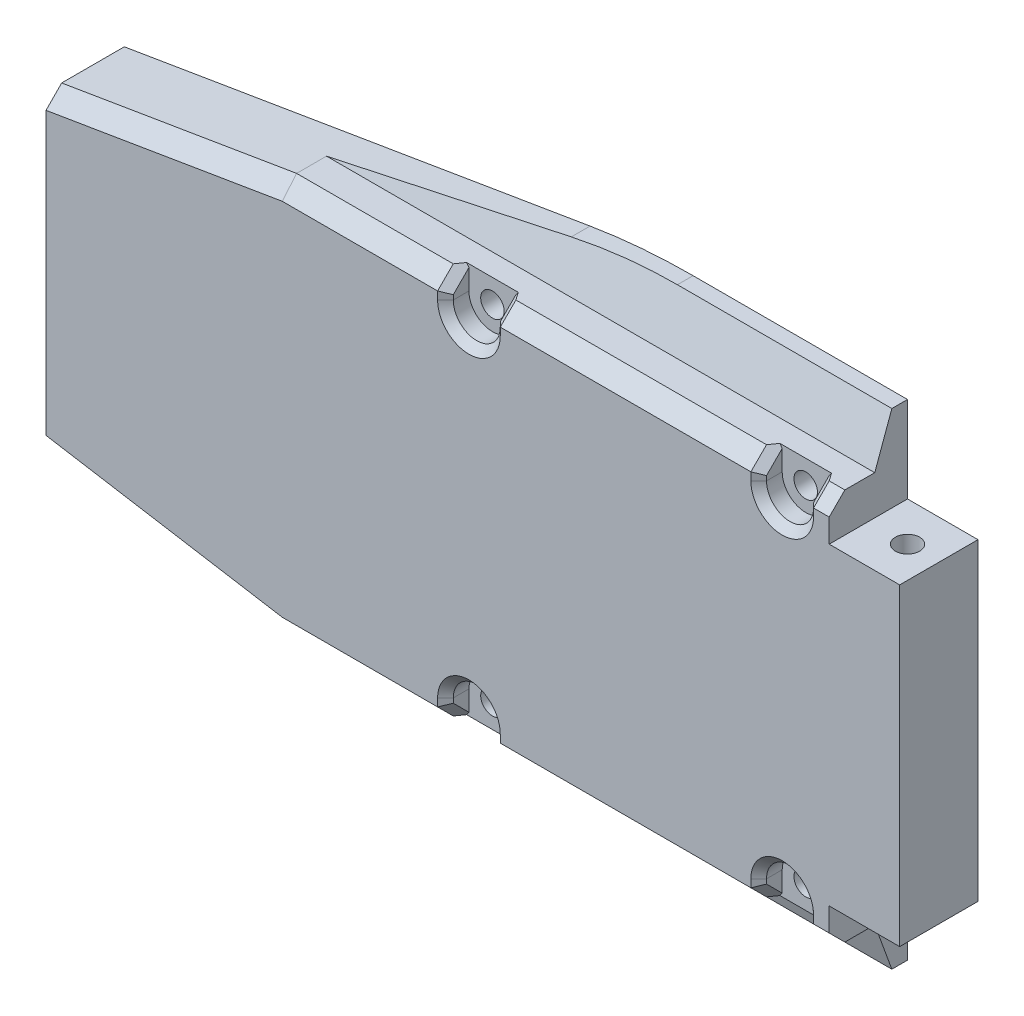
SolidWorks part; units mm, degrees
material "ABS"
ref_plane "Ebene vorne" through (0, 0, 0) normal (0, 0, 1) x (1, 0, 0)
ref_plane "Ebene oben" through (0, 0, 0) normal (0, 1, 0) x (1, 0, 0)
ref_plane "Ebene rechts" through (0, 0, 0) normal (1, 0, 0) x (0, 0, -1)
sketch "Skizze2" plane through (0, 0, 0) normal (0, 0, 1) x (1, 0, 0)
  line L0 (-151.7782, 0) -> (154.8922, 0) construction
  line L1 (0, 106.9611) -> (0, -93.0562) construction
  line L2 (0, 25) -> (-79, 25)
  line L3 (-79, 25) -> (-109, 20)
  line L4 (-109, 20) -> (-109, 11)
  line L5 (-109, 11) -> (-102, 11)
  line L6 (-99, 8) -> (-99, -8)
  line L7 (0, 25) -> (0, -25)
  line L8 (-109, -11) -> (-102, -11)
  line L9 (-109, -20) -> (-109, -11)
  line L10 (-79, -25) -> (-109, -20)
  line L11 (0, -25) -> (-79, -25)
  arc A0 (-102, -11) -> (-99, -8) centre (-102, -8) ccw
  arc A1 (-99, 8) -> (-102, 11) centre (-102, 8) ccw
  point P13 (0, 0)
  point P14 (-99, 0)
  point P19 (-99, -11)
  point P22 (-99, 11)
  dimension "D7" = 3
  dimension "D1" = 109
  dimension "D2" = 50
  dimension "D3" = 40
  dimension "D4" = 30
  dimension "D5" = 22
  dimension "D6" = 10
extrude "Aufsatz-Linear austragen1" add sketch "Skizze2" along normal blind 5 and the other way blind 5
hole_wizard "Ø3.1 (3.1) Durchmesser Bohrung1" positions "Skizze4" profile "Skizze3" hole size "Ø3.1" standard "ANSI Metrisch"
sketch "Skizze4" plane through (-109, 0, 0) normal (-1, 0, 0) x (0, 0, 1)
  line L0 (0, 37.8153) -> (0, -33.0973) construction
  line L3 (-22.117, 0) -> (22.0161, 0) construction
  point P0 (0, 15)
  point P14 (0, -15)
  dimension "D1" = 30
sketch "Skizze3" plane through (-109, 15, 0) normal (0, 1, 0) x (0, 0, 1)
  line L0 (0, 0) -> (0, 8.9313)
  line L1 (0, 8.9313) -> (1.55, 8)
  line L2 (1.55, 8) -> (1.55, 0)
  line L5 (1.55, 0) -> (0, 0)
  line L10 (0, 8.9313) -> (-1.55, 8) construction
  line L11 (0, -6.35) -> (0, 107.95) construction
  dimension "Bohrerdurchmesser" = 3.1
  dimension "Bohrungstiefe" = 8
  dimension "Spitzenwinkel" = 118
sketch "Skizze5" plane through (0, 0, 0) normal (0, 0, 1) x (1, 0, 0)
  line L0 (-134.3407, 0) -> (33.9152, 0) construction
  line L1 (0, 49.9151) -> (0, -37.4044) construction
  circle A0 centre (-55, 22) radius 1.5
  circle A1 centre (-15, 22) radius 1.5
  circle A2 centre (-15, -22) radius 1.5
  circle A3 centre (-55, -22) radius 1.5
  dimension "D1" = 3
  dimension "D2" = 40
  dimension "D3" = 15
  dimension "D4" = 22
extrude "Schnitt-Linear austragen1" cut sketch "Skizze5" against normal through all and the other way through all
sketch "Skizze6" plane through (0, 0, 5) normal (0, 0, 1) x (1, 0, 0)
  line L0 (-55, 22) -> (-55, 29.2626) construction
  line L1 (-58, 22) -> (-58, 29.2626)
  line L2 (-52, 22) -> (-52, 29.2626)
  line L3 (-15, 22) -> (-15, 29.2626) construction
  line L4 (-18, 22) -> (-18, 29.2626)
  line L5 (-12, 22) -> (-12, 29.2626)
  line L6 (-55, -22) -> (-55, -29.7807) construction
  line L7 (-52, -22) -> (-52, -29.7807)
  line L8 (-58, -22) -> (-58, -29.7807)
  line L9 (-15, -22) -> (-15, -30.8486) construction
  line L10 (-12, -22) -> (-12, -30.8486)
  line L11 (-18, -22) -> (-18, -30.8486)
  arc A4 (-58, 22) -> (-52, 22) centre (-55, 22) ccw
  arc A5 (-52, 29.2626) -> (-58, 29.2626) centre (-55, 29.2626) ccw
  arc A6 (-18, 22) -> (-12, 22) centre (-15, 22) ccw
  arc A7 (-12, 29.2626) -> (-18, 29.2626) centre (-15, 29.2626) ccw
  arc A8 (-52, -22) -> (-58, -22) centre (-55, -22) ccw
  arc A9 (-58, -29.7807) -> (-52, -29.7807) centre (-55, -29.7807) ccw
  arc A10 (-12, -22) -> (-18, -22) centre (-15, -22) ccw
  arc A11 (-18, -30.8486) -> (-12, -30.8486) centre (-15, -30.8486) ccw
  point P6 (-15, 25.6313)
  point P12 (-55, 25.6313)
  point P19 (-55, -25.8903)
  point P28 (-15, -26.4243)
  dimension "D1" = 3
extrude "Schnitt-Linear austragen2" cut sketch "Skizze6" against normal blind 3
sketch "Skizze7" plane through (0, 0, 5) normal (0, 0, 1) x (1, 0, 0)
  line L0 (-130.6386, 0) -> (13.2343, 0) construction
  line L1 (0, 46.5959) -> (0, -35.1065) construction
  line L2 (0, 25) -> (-9, 25)
  line L3 (0, 25) -> (-12, 25) construction
  line L4 (-9, 25) -> (-9, 20)
  line L5 (-9, 20) -> (0, 20)
  line L6 (0, 20) -> (0, 25)
  line L7 (0, -20) -> (0, -25)
  line L8 (-9, -20) -> (0, -20)
  line L9 (-9, -25) -> (-9, -20)
  line L10 (0, -25) -> (-9, -25)
  dimension "D1" = 5
  dimension "D2" = 9
extrude "Schnitt-Linear austragen3" cut sketch "Skizze7" against normal through all and the other way through all
sketch "Skizze8" plane through (0, 0, 0) normal (0, 0, 1) x (1, 0, 0)
  line L0 (-143.7875, 0) -> (29.5748, 0) construction
  line L1 (0, 40.8512) -> (0, -33.9576) construction
  line L17 (-55, 30.597) -> (-55, -26.6464) construction
  line L18 (-51, -22) -> (-19, -22)
  line L19 (-56, 18.127) -> (-56, -18.127)
  line L20 (-54, 18.127) -> (-54, -18.127)
  line L21 (-59, -22) -> (-78.7517, -22)
  line L22 (-78.7517, -22) -> (-97, -18.9586)
  line L23 (-97, -18.9586) -> (-97, 18.9586)
  line L24 (-79, -25) -> (-58, -25) construction
  line L25 (-109, -20) -> (-79, -25) construction
  line L26 (-99, 8) -> (-99, -8) construction
  line L27 (-78.7517, 22) -> (-97, 18.9586)
  line L28 (-59, 22) -> (-78.7517, 22)
  line L29 (-51, 22) -> (-19, 22)
  line L30 (-15, -18) -> (-7, -18)
  line L31 (-7, -18) -> (-7, 18)
  line L32 (-15, 18) -> (-7, 18)
  arc A6 (-56, -18.127) -> (-59, -22) centre (-55, -22) ccw
  arc A7 (-54, -18.127) -> (-51, -22) centre (-55, -22) cw
  arc A8 (-54, 18.127) -> (-51, 22) centre (-55, 22) ccw
  arc A9 (-56, 18.127) -> (-59, 22) centre (-55, 22) cw
  arc A10 (-19, -22) -> (-15, -18) centre (-15, -22) cw
  arc A11 (-19, 22) -> (-15, 18) centre (-15, 22) ccw
  point P16 (-56, 0)
  point P29 (-97, 0)
  point P30 (-54, 0)
  point P41 (-7, 0)
  dimension "D3" = 4
  dimension "D1" = 2
  dimension "D2" = 3
  dimension "D4" = 2
  dimension "D5" = 3
  dimension "D6" = 7
extrude "Schnitt-Linear austragen4" cut sketch "Skizze8" against normal through all and the other way blind 4
sketch "Skizze9" plane through (0, 0, -5) normal (0, 0, -1) x (-1, 0, 0)
  line L0 (-28.3161, 0) -> (120.4033, 0) construction
  line L1 (0, 48.4649) -> (0, -32.3525) construction
  line L2 (9, 25) -> (9, 31)
  line L3 (9, 31) -> (43, 31)
  line L7 (9, 25) -> (79, 25)
  line L8 (9, -25) -> (79, -25)
  line L11 (9, -31) -> (43, -31)
  line L12 (9, -25) -> (9, -31)
  line L13 (43, 31) -> (79, 25)
  line L14 (43, -31) -> (79, -25)
  line L15 (79, 25) -> (109, 20) construction
  dimension "D1" = 6
extrude "Aufsatz-Linear austragen2" add sketch "Skizze9" against normal blind 2
hole_wizard "Ø3.1 (3.1) Durchmesser Bohrung2" positions "Skizze11" profile "Skizze10" hole size "Ø3.1" standard "ANSI Metrisch"
sketch "Skizze11" plane through (0, 20, 0) normal (0, 1, 0) x (1, 0, 0)
  line L0 (14.2177, 0) -> (-26.5383, 0) construction
  point P0 (-4, 0)
  dimension "D1" = 4
sketch "Skizze10" plane through (-4, 20, 0) normal (1, 0, 0) x (0, 0, 1)
  line L0 (0, 0) -> (0, 10.9313)
  line L1 (0, 10.9313) -> (1.55, 10)
  line L2 (1.55, 10) -> (1.55, 0)
  line L5 (1.55, 0) -> (0, 0)
  line L10 (0, 10.9313) -> (-1.55, 10) construction
  line L11 (0, -6.35) -> (0, 107.95) construction
  dimension "Bohrerdurchmesser" = 3.1
  dimension "Bohrungstiefe" = 10
  dimension "Spitzenwinkel" = 118
mirror "Spiegeln1" about plane through (0, 0, 0) normal (0, 1, 0) of "Ø3.1 (3.1) Durchmesser Bohrung2"
chamfer "Fase1" distance 6 angle 20 1 edges at (-44, 25, -3) first distance on face at (-35, 28, -3)
chamfer "Fase2" distance 6 angle 20 1 edges at (-44, -25, -3) first distance on face at (-35, -28, -3)
fillet "Verrundung1" radius 80 2 edges at (-43, 31, -4) (-43, -31, -4)
fillet "Verrundung2" radius 2 14 edges at (-7, 18, -0.5) (-19, 22, -0.5) (-51, 22, -0.5) (-54, 18.127, -0.5) (-56, 18.127, -0.5) (-59, 22, -0.5) (-97, 18.9586, -0.5) (-97, -18.9586, -0.5) (-59, -22, -0.5) (-56, -18.127, -0.5) (-54, -18.127, -0.5) (-51, -22, -0.5) (-19, -22, -0.5) (-7, -18, -0.5)
sketch "Skizze12" plane through (0, 0, 5) normal (0, 0, 1) x (1, 0, 0)
  line L0 (-110.4008, 0) -> (7.7355, 0) construction
  line L1 (0, 42.6084) -> (0, -37.939) construction
  line L2 (-109, 11) -> (-109, -11)
  line L3 (-109, -11) -> (-99, -11)
  line L4 (-99, -11) -> (-99, 11)
  line L5 (-99, 11) -> (-109, 11)
  line L6 (-109, 20) -> (-109, 11) construction
  line L7 (-99, 8) -> (-99, -8) construction
extrude "Aufsatz-Linear austragen3" add sketch "Skizze12" against normal blind 1
chamfer "Fase3" distance 2 angle 45 8 edges at (-10.5, -25, 5) (-35, -25, 5) (-68.5, -25, 5) (-94, -22.5, 5) (-10.5, 25, 5) (-35, 25, 5) (-68.5, 25, 5) (-94, 22.5, 5)
fillet "Verrundung3" [suppressed] radius 1.5
sketch "Skizze13" plane through (0, 0, -5) normal (0, 0, -1) x (-1, 0, 0)
  line L0 (4, 10) -> (4, -10) construction
  line L1 (5.5, 10) -> (5.5, -10)
  line L2 (2.5, 10) -> (2.5, -10)
  line L3 (-14.13, 0) -> (38.0816, 0) construction
  arc A0 (5.5, 10) -> (2.5, 10) centre (4, 10) ccw
  arc A1 (2.5, -10) -> (5.5, -10) centre (4, -10) ccw
  point P4 (4, 0)
  dimension "D1" = 3
  dimension "D2" = 4
  dimension "D3" = 20
extrude "Schnitt-Linear austragen5" cut sketch "Skizze13" against normal up to surface (9 mm away) up to face at (-30.8946, 0, 4)
chamfer "Fase4" distance 1 angle 45 20 edges at (-12, -24, 4) (-18, -24, 4) (-12, -22.5, 5) (-18, -22.5, 5) (-15, -19, 5) (-58, 24, 4) (-52, 24, 4) (-58, 22.5, 5) (-52, 22.5, 5) (-55, 19, 5) (-18, 24, 4) (-12, 24, 4) (-18, 22.5, 5) (-12, 22.5, 5) (-15, 19, 5) (-52, -22.5, 5) (-58, -22.5, 5) (-55, -19, 5) (-58, -24, 4) (-52, -24, 4)
ref_axis "Achse1" through (-110.25, 0, 0) along (1, 0, 0)
ref_axis "Achse2" through (0, 0, -5.5) along (0, 0, 1)
ref_axis "Achse3" through (0, 34.1, 0) along (0, -1, 0)
